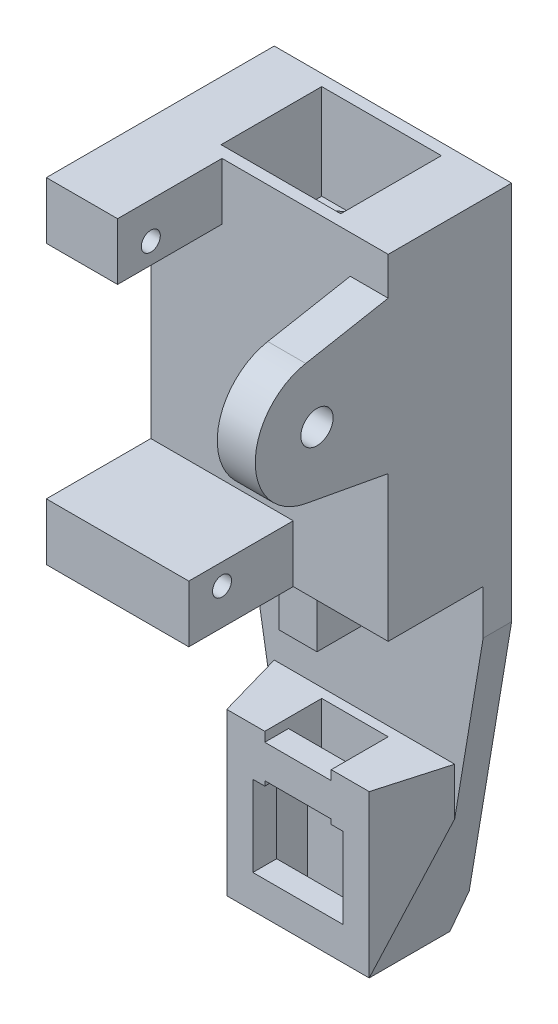
SolidWorks part; units mm, degrees
ref_plane "Plano frontal" through (0, 0, 0) normal (0, 0, 1) x (1, 0, 0)
ref_plane "Plano superior" through (0, 0, 0) normal (0, 1, 0) x (1, 0, 0)
ref_plane "Plano direito" through (0, 0, 0) normal (1, 0, 0) x (0, 0, -1)
sketch "Esboço1" plane through (0, 0, 0) normal (0, 0, 1) x (1, 0, 0)
  line L0 (-12.5, 0) -> (12.5, 0)
  line L1 (12.5, 0) -> (12.5, -40)
  line L2 (12.5, -40) -> (7.5, -70)
  line L3 (7.5, -70) -> (-7.5, -70)
  line L4 (-7.5, -70) -> (-12.5, -40)
  line L5 (-12.5, -40) -> (-12.5, 0)
  point P3 (0, -70)
  point P7 (0, 0)
  dimension "D1" = 40
  dimension "D2" = 30
  dimension "D3" = 25
  dimension "D4" = 15
extrude "Ressalto-extrusão1" add sketch "Esboço1" along normal blind 13
sketch "Esboço2" plane through (0, 0, 13) normal (0, 0, 1) x (1, 0, 0)
  line L1 (2.5, -35.3) -> (-12.5, -35.3)
  line L2 (2.5, -35.3) -> (2.5, -29.3)
  line L3 (2.5, -29.3) -> (-12.5, -29.3)
  line L4 (-12.5, -35.3) -> (-12.5, -29.3)
  line L5 (-12.5, 0) -> (2.5, 0)
  line L6 (-12.5, 0) -> (-12.5, -6)
  line L7 (-12.5, -6) -> (2.5, -6)
  line L8 (2.5, 0) -> (2.5, -6)
  line L11 (12.5, -4) -> (8.5, -4)
  line L12 (12.5, -4) -> (12.5, -20)
  line L13 (12.5, -20) -> (8.5, -20)
  line L14 (8.5, -4) -> (8.5, -20)
  line L15 (-12.5, -6) -> (-12.5, -29.3) construction
  line L16 (-12.5, -28.9) -> (-12.5, -6.4) construction
  point P16 (8.5, -12)
  point P21 (-12.5, -17.65)
  dimension "D1" = 23.3
  dimension "D2" = 6
  dimension "D3" = 15
  dimension "D4" = 21
  dimension "D6" = 22.5
  dimension "D7" = 5.65
  dimension "D8" = 16
  dimension "D9" = 4
extrude "Ressalto-extrusão2" add sketch "Esboço2" along normal blind 15
sketch "Esboço3" plane through (2.5, 0, 0) normal (1, 0, 0) x (0, 0, -1)
  line L0 (-28, -6) -> (-28, -29.3) construction
  line L1 (-28, -17.65) -> (-13, -17.65) construction
  line L2 (-13, -40) -> (-13, -20) construction
  line L3 (-28, -6) -> (-13, -6) construction
  line L4 (-28, 0) -> (-9, 0) construction
  line L5 (-28, 0) -> (-13, 0) construction
  line L6 (-28, -20) -> (-28, -4) construction
  circle A0 centre (-20.5, -3.8) radius 1
  circle A3 centre (-20.5, -31.5) radius 1
  circle A5 centre (-20.5, -12) radius 1.75
  point P24 (-20.5, -6)
  point P31 (-28, -12)
  dimension "D1" = 2
  dimension "D5" = 3.5
  dimension "D2" = 27.7
extrude "Corte-extrusão1" cut sketch "Esboço3" against normal through all contours A5 | A0 | A3 region at (2.5, -3.8, 20.5) region at (2.5, -12, 20.5)
sketch "Esboço10" plane through (12.5, 0, 0) normal (1, 0, 0) x (0, 0, -1)
  line L0 (-28, -20) -> (-28, -4) construction
  line L1 (-20.5, -3.8) -> (-20.5, -31.5) construction
  line L2 (-13, -4) -> (-28, -4)
  line L3 (-28, -4) -> (-28, -20)
  line L4 (-28, -20) -> (-13, -20)
  line L5 (-13, -4) -> (-21.684, -5.6087)
  line L6 (-13, -20) -> (-21.684, -18.3913)
  circle A0 centre (-20.5, -12) radius 1.7
  arc A2 (-21.684, -5.6087) -> (-21.684, -18.3913) centre (-20.5, -12) ccw
  point P5 (-28, -12)
  dimension "D1" = 3.4
  dimension "D2" = 6.5
extrude "Corte-extrusão4" cut sketch "Esboço10" against normal blind 10
sketch "Esboço11" plane through (0, 0, 13) normal (0, 0, 1) x (1, 0, 0)
  line L0 (12.5, -40) -> (12.5, -20) construction
  line L1 (-12.5, -35.3) -> (12.5, -35.3)
  line L2 (-12.5, -35.3) -> (-12.5, -70)
  line L3 (-12.5, -70) -> (12.5, -70)
  line L4 (12.5, -35.3) -> (12.5, -70)
  line L5 (-7.5, -70) -> (7.5, -70) construction
extrude "Corte-extrusão5" cut sketch "Esboço11" against normal blind 10
sketch "Esboço6" plane through (0, -70, 0) normal (0, -1, 0) x (1, 0, 0)
  line L0 (-5, 4) -> (-5, 7.5)
  line L1 (-5, 7.5) -> (-4.75, 7.5)
  line L2 (-4.75, 7.5) -> (-4.75, 10)
  line L3 (-4.75, 10) -> (-7.5, 10)
  line L4 (-7.5, 10) -> (-7.5, 3)
  line L7 (0, 13) -> (0, 11.0668) construction
  line L8 (-7.5, 13) -> (7.5, 13) construction
  line L10 (7.5, 10) -> (7.5, 3)
  line L11 (4.75, 10) -> (7.5, 10)
  line L12 (4.75, 7.5) -> (4.75, 10)
  line L13 (5, 7.5) -> (4.75, 7.5)
  line L14 (5, 4) -> (5, 7.5)
  line L15 (-7.5, 3) -> (7.5, 3)
  line L16 (5, 4) -> (-5, 4)
  dimension "D2" = 9.5
  dimension "D3" = 3.5
  dimension "D4" = 1
  dimension "D5" = 6
  dimension "D6" = 10
extrude "Ressalto-extrusão3" add sketch "Esboço6" against normal blind 17
sketch "Esboço7" plane through (0, 0, 3) normal (0, 0, 1) x (1, 0, 0)
  line L0 (-7.5, -70) -> (7.5, -70) construction
  line L1 (2, -38) -> (-2, -38)
  line L2 (2, -38) -> (2, -43)
  line L3 (2, -43) -> (-2, -43)
  line L4 (-2, -38) -> (-2, -43)
  line L5 (2, -38) -> (-2, -43) construction
  line L6 (2, -43) -> (-2, -38) construction
  line L7 (-7.5, -53) -> (-5, -53) construction
  line L8 (5, -53) -> (7.5, -53) construction
  line L9 (7.5, -58) -> (3.5, -58)
  line L10 (7.5, -58) -> (7.5, -53)
  line L11 (7.5, -53) -> (3.5, -53)
  line L12 (3.5, -58) -> (3.5, -53)
  line L13 (7.5, -58) -> (3.5, -53) construction
  line L14 (7.5, -53) -> (3.5, -58) construction
  line L15 (-3.5, -58) -> (-7.5, -58)
  line L16 (-3.5, -58) -> (-3.5, -53)
  line L17 (-3.5, -53) -> (-7.5, -53)
  line L18 (-7.5, -58) -> (-7.5, -53)
  line L19 (-3.5, -58) -> (-7.5, -53) construction
  line L20 (-3.5, -53) -> (-7.5, -58) construction
  line L21 (7.5, -53) -> (7.5, -70) construction
  line L22 (7.5, -53) -> (7.5, -70) construction
  line L23 (-7.5, -53) -> (-7.5, -70) construction
  line L24 (-7.5, -53) -> (-7.5, -70) construction
  point P0 (0, -40.5)
  point P5 (-5.5, -55.5)
  point P8 (0, -70)
  point P11 (5.5, -55.5)
  dimension "D1" = 4
  dimension "D2" = 5
  dimension "D3" = 10
  dimension "D4" = 7
  dimension "D5" = 5
  dimension "D6" = 0
extrude "Ressalto-extrusão4" add sketch "Esboço7" along normal up to surface (7 mm away) up to face at (-6.125, -61.5, 10)
sketch "Esboço8" plane through (0, 0, 10) normal (0, 0, 1) x (1, 0, 0)
  line L0 (-7.5, -70) -> (7.5, -70)
  line L1 (7.5, -70) -> (7.5, -66.5)
  line L2 (7.5, -53) -> (7.5, -70) construction
  line L3 (7.5, -66.5) -> (-7.5, -66.5)
  line L4 (-7.5, -53) -> (-7.5, -70) construction
  line L5 (-7.5, -66.5) -> (-7.5, -70)
  line L7 (7.5, -54) -> (-7.5, -54)
  line L8 (7.5, -54) -> (7.5, -57.5)
  line L9 (7.5, -57.5) -> (-7.5, -57.5)
  line L10 (-7.5, -54) -> (-7.5, -57.5)
  dimension "D1" = 3.5
  dimension "D2" = 9
extrude "Ressalto-extrusão5" add sketch "Esboço8" against normal up to surface (2.5 mm away) up to face at (4.875, -64, 7.5)
chamfer "Chanfro2" distance 2 distance2 7 2 edges at (7.5, -61.5, 3) (-7.5, -61.5, 3) first distance on face at (0, -49.575, 3)
chamfer "Chanfro3" distance 1.5 angle 65 1 edges at (0, -70, 0) first distance on face at (0, -70, 5)
sketch "Esboço12" plane through (0, 0, 0) normal (0, 1, 0) x (1, 0, 0)
  line L0 (12.5, -13) -> (12.5, 0) construction
  line L1 (6.3, -11.8) -> (-6.3, -11.8)
  line L2 (6.3, -11.8) -> (6.3, -1.2)
  line L3 (6.3, -1.2) -> (-6.3, -1.2)
  line L4 (-6.3, -11.8) -> (-6.3, -1.2)
  line L5 (6.3, -11.8) -> (-6.3, -1.2) construction
  line L6 (6.3, -1.2) -> (-6.3, -11.8) construction
  point P0 (0, -6.5)
  point P10 (12.5, -6.5)
  dimension "D1" = 10.6
  dimension "D2" = 12.6
extrude "Corte-extrusão6" cut sketch "Esboço12" against normal blind 10
sketch "Esboço13" plane through (0, -10, 0) normal (0, 1, 0) x (1, 0, 0)
  line L0 (-6.3, -1.2) -> (-6.3, -11.8) construction
  line L1 (-6.3, -11.8) -> (6.3, -11.8) construction
  line L2 (-3.4059, -11.8) -> (3.4059, -11.8)
  line L3 (-3.4059, -1.2) -> (3.4059, -1.2)
  line L4 (6.3, -1.2) -> (-6.3, -1.2) construction
  arc A0 (-3.4059, -1.2) -> (-3.4059, -11.8) centre (0, -6.5) ccw
  arc A1 (3.4059, -11.8) -> (3.4059, -1.2) centre (0, -6.5) ccw
  point P5 (-6.3, -6.5)
  point P8 (0, -11.8)
  dimension "D1" = 12.6
  dimension "D2" = 10.6
extrude "Corte-extrusão7" cut sketch "Esboço13" against normal blind 22
sketch "Esboço15" plane through (-12.5, 0, 0) normal (-1, 0, 0) x (0, 0, 1)
  line L0 (0, 0) -> (0, -40) construction
  line L1 (28, 0) -> (0, 0) construction
  circle A0 centre (6, -28) radius 2
  dimension "D1" = 4
  dimension "D2" = 6
  dimension "D3" = 28
extrude "Corte-extrusão9" cut sketch "Esboço15" against normal blind 15
sketch "Esboço17" plane through (0, 0, 28) normal (0, 0, 1) x (1, 0, 0)
  line L1 (2.5, 0) -> (-12.5, 0)
  line L2 (2.5, 0) -> (2.5, -35.3)
  line L3 (2.5, -35.3) -> (-12.5, -35.3)
  line L4 (-12.5, 0) -> (-12.5, -35.3)
extrude "Corte-extrusão10" cut sketch "Esboço17" against normal blind 4
sketch "Esboço18" plane through (0, 0, 24) normal (0, 0, 1) x (1, 0, 0)
  line L0 (2.5, 0) -> (-12.5, 0) construction
  line L1 (2.5, -6) -> (-5, -6)
  line L2 (2.5, -6) -> (2.5, 0)
  line L3 (2.5, 0) -> (-5, 0)
  line L4 (-5, -6) -> (-5, 0)
extrude "Corte-extrusão11" cut sketch "Esboço18" against normal up to surface (11 mm away) up to face at (4.3333, -15.7667, 13)
